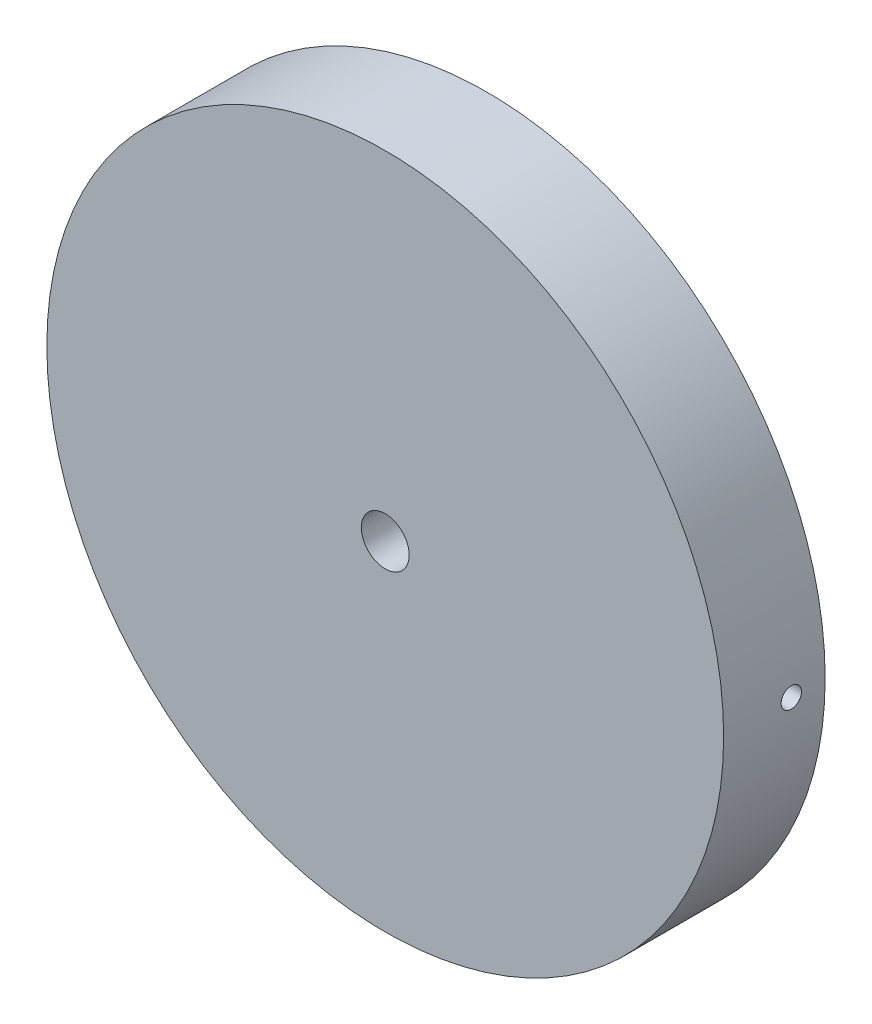
SolidWorks part; units mm, degrees
ref_plane "Front Plane" through (0, 0, 0) normal (0, 0, 1) x (1, 0, 0)
ref_plane "Top Plane" through (0, 0, 0) normal (0, 1, 0) x (1, 0, 0)
ref_plane "Right Plane" through (0, 0, 0) normal (1, 0, 0) x (0, 0, -1)
ref_axis "Z" through (0, 0, 543.0939) along (0, 0, -1)
ref_axis "X" through (17.0818, 0, 0) along (-1, 0, 0)
ref_axis "Y" through (0, 20.242, 0) along (0, -1, 0)
sketch "Sketch1" plane through (0, 0, 0) normal (0, 0, 1) x (1, 0, 0)
  circle A0 centre (0, 0) radius 50
  circle A1 centre (0, 0) radius 3.535
  dimension "D1" = 100
  dimension "D2" = 7.07
extrude "Boss-Extrude1" add sketch "Sketch1" against normal blind 5 and the other way blind 10
sketch "Sketch2" plane through (0, 0, 0) normal (0, 1, 0) x (1, 0, 0)
  line L0 (-16.3173, 0) -> (16.3173, 0) construction
  line L1 (0, -20.5521) -> (0, 20.5521) construction
  circle A0 centre (0, 0) radius 1.5
  dimension "D1" = 3
extrude "Cut-Extrude1" cut sketch "Sketch2" against normal through all
sketch "Sketch3" plane through (0, 0, 0) normal (1, 0, 0) x (0, 0, -1)
  circle A0 centre (0, 0) radius 1.5
  dimension "D1" = 3
extrude "Cut-Extrude2" cut sketch "Sketch3" along normal through all
sketch "Sketch4" plane through (0, 0, 0) normal (0, 0, 1) x (1, 0, 0)
  circle A0 centre (0, 0) radius 3.535
  circle A2 centre (0, 0) radius 3.535 construction
  circle A3 centre (0, 0) radius 35
  dimension "D1" = 70
extrude "Boss-Extrude2" add sketch "Sketch4" along normal up to surface and the other way up to surface up to face at (50, 0, 10) other way up to face at (3.535, 0, -5)
sketch "Sketch5" plane through (0, 0, 0) normal (0, 0, 1) x (1, 0, 0)
  line L0 (0, 0) -> (0, -67) construction
  dimension "D1" = 67
ref_plane "Vert" through (0, 0, 0) normal (0.7071, 0.7071, 0) x (0, 0, -1)
equation "\"EyeDiameter\" = 100"
equation "\"BasePlaneDistance\" = \"EyeDiameter\"/2+\"L2Thickness\"+\"EyeClearance\""
equation "\"EyeClearance\" = 2"
equation "\"EyeOD\"= \"EyeDiameter\""
equation "\"D1@Sketch1\"=\"EyeOD\""
equation "\"D2@Sketch1\"= 7.07"
equation "\"pinHoleDiameter\"= 3"
equation "\"D1@Sketch2\"=\"pinHoleDiameter\""
equation "\"D1@Sketch3\"=\"pinHoleDiameter\""
equation "\"D1@Sketch4\"=\"EyeDiameter\"-30"
equation "\"D1@Sketch5\"=\"BasePlaneDistance\""
